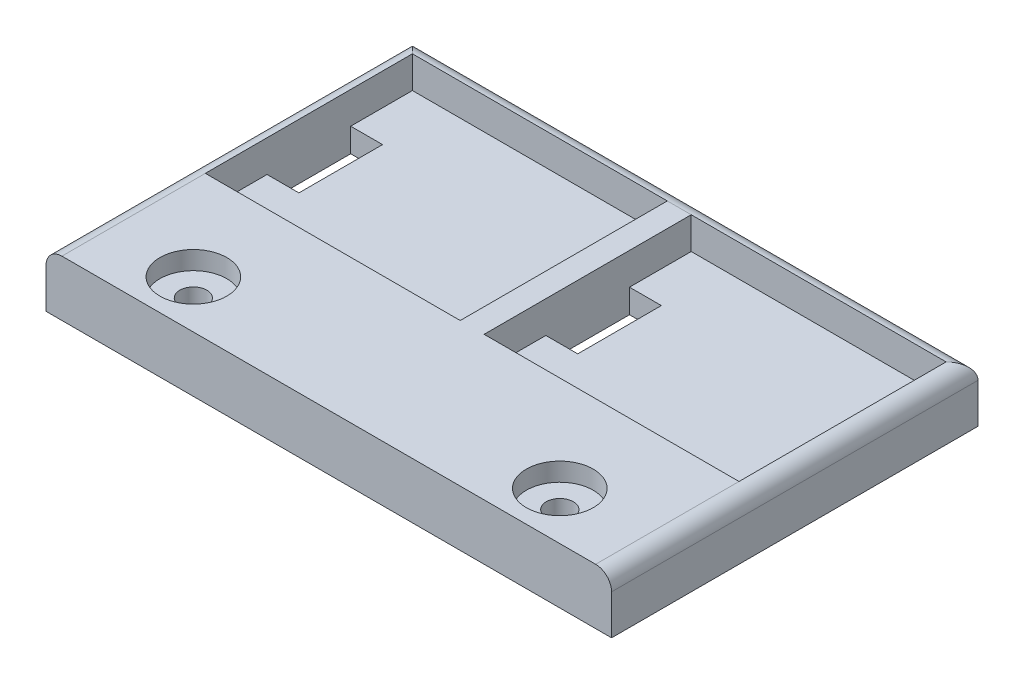
SolidWorks part; units mm, degrees
ref_plane "Front Plane" through (0, 0, 0) normal (0, 0, 1) x (1, 0, 0)
ref_plane "Top Plane" through (0, 0, 0) normal (0, 1, 0) x (1, 0, 0)
ref_plane "Right Plane" through (0, 0, 0) normal (1, 0, 0) x (0, 0, -1)
sketch "Sketch1" plane through (0, 0, 0) normal (0, 1, 0) x (1, 0, 0)
  line L0 (0, 23) -> (0, -23) construction
  line L1 (-35.5, -23) -> (35.5, -23)
  line L2 (-35.5, -23) -> (-35.5, 23)
  line L3 (-35.5, 23) -> (35.5, 23)
  line L4 (35.5, -23) -> (35.5, 23)
  line L5 (-35.5, -23) -> (35.5, 23) construction
  line L6 (-35.5, 23) -> (35.5, -23) construction
  line L7 (-33.5, -5) -> (-1.5, -5)
  line L8 (-33.5, -5) -> (-33.5, 21)
  line L9 (-33.5, 21) -> (-1.5, 21)
  line L10 (-1.5, -5) -> (-1.5, 21)
  line L11 (-33.5, -5) -> (-1.5, 21) construction
  line L12 (-33.5, 21) -> (-1.5, -5) construction
  line L13 (33.5, 21) -> (1.5, 21)
  line L14 (1.5, -5) -> (1.5, 21)
  line L15 (33.5, -5) -> (1.5, -5)
  line L16 (33.5, -5) -> (33.5, 21)
  point P0 (0, 0)
  point P6 (-17.5, 8)
  dimension "D1" = 46
  dimension "D2" = 71
  dimension "D3" = 32
  dimension "D4" = 26
  dimension "D5" = 2
  dimension "D6" = 2
extrude "Boss-Extrude1" add sketch "Sketch1" along normal blind 7
extrude "Boss-Extrude2" add sketch "Sketch1<2>" along normal blind 3 contours L7 L10 L9 L8 | L14 L13 L16 L15 region at (-17.5, 0, -8)
sketch "Sketch1<2>" plane through (0, 0, 0) normal (0, 1, 0) x (1, 0, 0) same geometry as "Sketch1"
hole_wizard "CBORE for M3 Hex Head Machine Screw1" positions "Sketch4" profile "Sketch5" counterbore size "M3" standard "ANSI Metric" end condition through all
sketch "Sketch4" plane through (0, 7, 0) normal (0, 1, 0) x (1, 0, 0)
  line L0 (0, 23) -> (0, -23) construction
  line L1 (35.5, 23) -> (-35.5, 23) construction
  line L2 (-35.5, -23) -> (35.5, -23) construction
  point P0 (-23, -17)
  point P10 (0, 0)
  point P11 (23, -17)
  dimension "D1" = 46
  dimension "D2" = 6
sketch "Sketch5" plane through (-23, 7, 17) normal (1, 0, 0) x (0, 0, 1)
  line L0 (0, 0) -> (0, 7)
  line L1 (0, 7) -> (1.7, 7)
  line L3 (1.7, 7) -> (1.7, 2.3)
  line L4 (1.7, 2.3) -> (4.2, 2.3)
  line L5 (4.2, 2.3) -> (4.2, 0)
  line L7 (4.2, 0) -> (0, 0)
  line L11 (0, -6.35) -> (0, 107.95) construction
  dimension "Thru Hole Dia." = 3.4
  dimension "Thru Hole Depth" = 7
  dimension "C'Bore Dia." = 8.4
  dimension "C'Bore Depth" = 2.3
sketch "Sketch6" plane through (0, 3, 0) normal (0, 1, 0) x (1, 0, 0)
  line L0 (-33.5, -5) -> (-33.5, 21) construction
  line L1 (-33.5, 13.25) -> (-29.5, 13.25)
  line L2 (-33.5, 13.25) -> (-33.5, 2.75)
  line L3 (-33.5, 2.75) -> (-29.5, 2.75)
  line L4 (-29.5, 13.25) -> (-29.5, 2.75)
  line L5 (-17.5, 21) -> (-17.5, -5) construction
  line L6 (-33.5, 21) -> (-1.5, 21) construction
  line L7 (-33.5, -5) -> (-1.5, -5) construction
  line L8 (0, 23) -> (0, -23) construction
  line L9 (35.5, 23) -> (-35.5, 23) construction
  line L10 (-35.5, -23) -> (35.5, -23) construction
  line L11 (-1.5, 8) -> (-33.5, 8) construction
  line L12 (-1.5, -5) -> (-1.5, 21) construction
  line L13 (-33.5, 21) -> (-33.5, -5) construction
  line L15 (-1.5, 2.75) -> (-5.5, 2.75)
  line L16 (-5.5, 13.25) -> (-5.5, 2.75)
  line L17 (-1.5, 13.25) -> (-5.5, 13.25)
  line L18 (-1.5, 13.25) -> (-1.5, 2.75)
  line L19 (1.5, 13.25) -> (1.5, 2.75)
  line L20 (1.5, 13.25) -> (5.5, 13.25)
  line L21 (5.5, 13.25) -> (5.5, 2.75)
  line L22 (1.5, 2.75) -> (5.5, 2.75)
  line L23 (33.5, 2.75) -> (29.5, 2.75)
  line L24 (29.5, 13.25) -> (29.5, 2.75)
  line L25 (33.5, 13.25) -> (29.5, 13.25)
  line L26 (33.5, 13.25) -> (33.5, 2.75)
  point P22 (0, 0)
  point P25 (-33.5, 8)
  dimension "D1" = 4
  dimension "D2" = 10.5
extrude "Cut-Extrude1" cut sketch "Sketch6" against normal through all
fillet "Fillet1" radius 2 3 edges at (35.5, 7, 0) (0, 7, -23) (-35.5, 7, 0)
